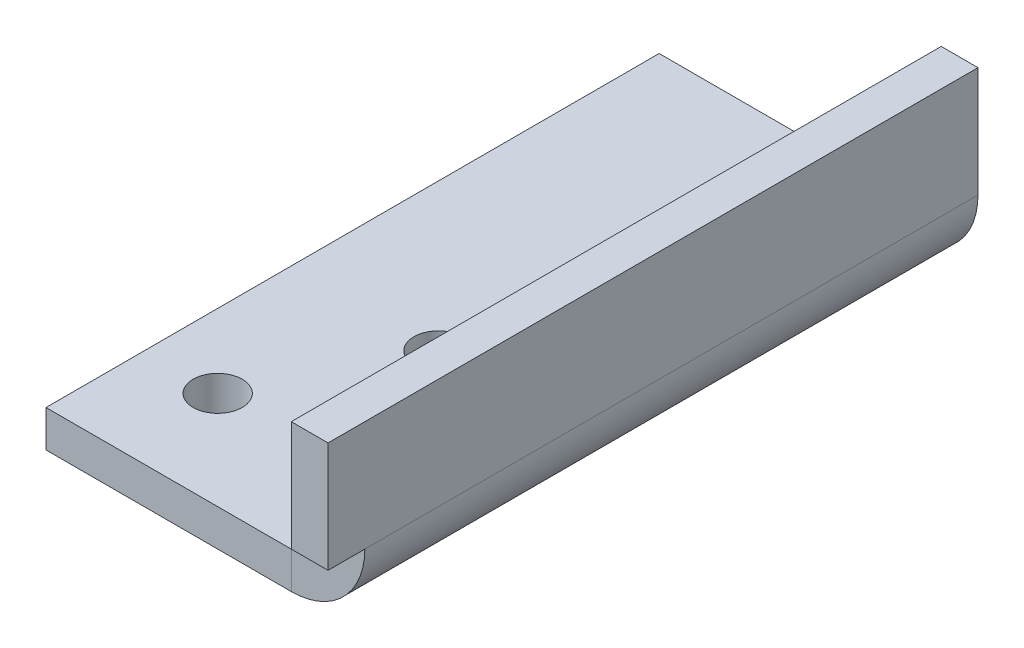
SolidWorks part; units mm, degrees
note: The reader was unsure of these and kept them because the rebuilt part matched: flange length of "Edge-Flange1".
ref_plane "Front Plane" through (0, 0, 0) normal (0, 0, 1) x (1, 0, 0)
ref_plane "Top Plane" through (0, 0, 0) normal (0, 1, 0) x (1, 0, 0)
ref_plane "Right Plane" through (0, 0, 0) normal (1, 0, 0) x (0, 0, -1)
sketch "Sketch1" plane through (0, 0, 0) normal (0, 1, 0) x (1, 0, 0)
  line L1 (-10, 25) -> (10, 25)
  line L2 (-10, 25) -> (-10, -25)
  line L3 (-10, -25) -> (10, -25)
  line L4 (10, 25) -> (10, -25)
  circle A0 centre (-4, 17) radius 2
  circle A1 centre (2, 5) radius 2
  dimension "D5" = 4
  dimension "D6" = 6
  dimension "D8" = 4
  dimension "D9" = 20
  dimension "D10" = 12
  dimension "D1" = 20
  dimension "D2" = 50
  dimension "D3" = 10
  dimension "D4" = 25
  dimension "D7" = 8
base flange "Base-Flange1" sketch "Sketch1" thickness 3 reverse thickness direction no parameters "D1"=0.7366
edge flange "Edge-Flange1" sketch "Sketch10" flange angle 90 flange length 15 flange position bend outside bend radius 3 thickness 3 parameters "D6"=10
sketch "Sketch10" plane through (10, 0, 0) normal (1, 0, 0) x (0, 0, -1)
  line L2 (-25, 0) -> (-25, 12)
  line L3 (-25, 12) -> (28, 12)
  line L7 (-25, 0) -> (25, 0) construction
  line L8 (-25, 0) -> (28, 0)
  line L9 (28, 12) -> (28, 0)
  dimension "D1" = 12
  dimension "D2" = 53
bend "EdgeBend1" bend radius 3 bend angle 90 parameters "D5"=1
mirror "Mirror1"
bend "DerivedBend1" bend radius 3 bend angle 90 parameters "D5"=3
bend "MirrorBend1" bend radius 3 bend angle 90 parameters "D5"=2
delete or keep bodies "Body-Delete/Keep 1" type delete bodies bodies 102
sketch "Bend-Lines1" [suppressed] plane through (0, 0, 0) normal (0, 1, 0) x (1, 0, 0)
sketch "Bounding-Box1" [suppressed] plane through (0, 0, 0) normal (0, 1, 0) x (1, 0, 0)
sheet metal parameters "Sheet-Metal1" thickness 3 parameters "D1"=0.7366
flat pattern "Flat-Pattern1" [suppressed]
sketch "Bend-Lines2" plane through (0, 0, 0) normal (0, 1, 0) x (1, 0, 0)
sketch3d "Bounding-Box2" [suppressed]
  line L0 (-10, 25, 0) -> (-10, -25, 0) construction
  line L1 (10, 25, 0) -> (10, -25, 0) construction
  line L2 (-10, 25, 0) -> (10, 25, 0) construction
  line L3 (-10, -25, 0) -> (10, -25, 0) construction
sheet metal parameters "Sheet-Metal2" thickness 3 parameters "D1"=0.7366
flat pattern "Flat-Pattern1"
sketch "Bend-Lines2" plane through (0, 0, 0) normal (0, 1, 0) x (1, 0, 0)
  line L0 (13.5343, -25) -> (13.5343, 25) construction
  line L1 (13.5343, -25) -> (13.5343, 25) construction
sketch3d "Bounding-Box2" [suppressed]
  line L0 (-10, 28, 0) -> (-10, -25, 0) construction
  line L1 (26.0686, 28, 0) -> (26.0686, -25, 0) construction
  line L2 (-10, 28, 0) -> (26.0686, 28, 0) construction
  line L3 (-10, -25, 0) -> (26.0686, -25, 0) construction
bend of the flat pattern "Flatten-<EdgeBend1>1"
sheet metal parameters "Sheet-Metal3" thickness 3 parameters "D1"=0.7366
flat pattern "Flat-Pattern3"
sketch "Bend-Lines3" plane through (0, -3, 0) normal (0, -1, 0) x (-1, 0, 0)
  line L4 (-13.5343, 31) -> (-13.5343, 81) construction
  line L5 (-13.5343, 31) -> (-13.5343, 81) construction
  point P0 (13.5343, 81)
  point P1 (13.5343, 31)
  point P2 (13.5343, -25)
  point P3 (13.5343, 25)
sketch3d "Bounding-Box3" [suppressed]
  line L0 (-26.0686, 25, 0) -> (-26.0686, -28, 0) construction
  line L1 (10, 25, 0) -> (10, -28, 0) construction
  line L2 (-26.0686, 25, 0) -> (10, 25, 0) construction
  line L3 (-26.0686, -28, 0) -> (10, -28, 0) construction
bend of the flat pattern "Flatten-<DerivedBend1>1"
